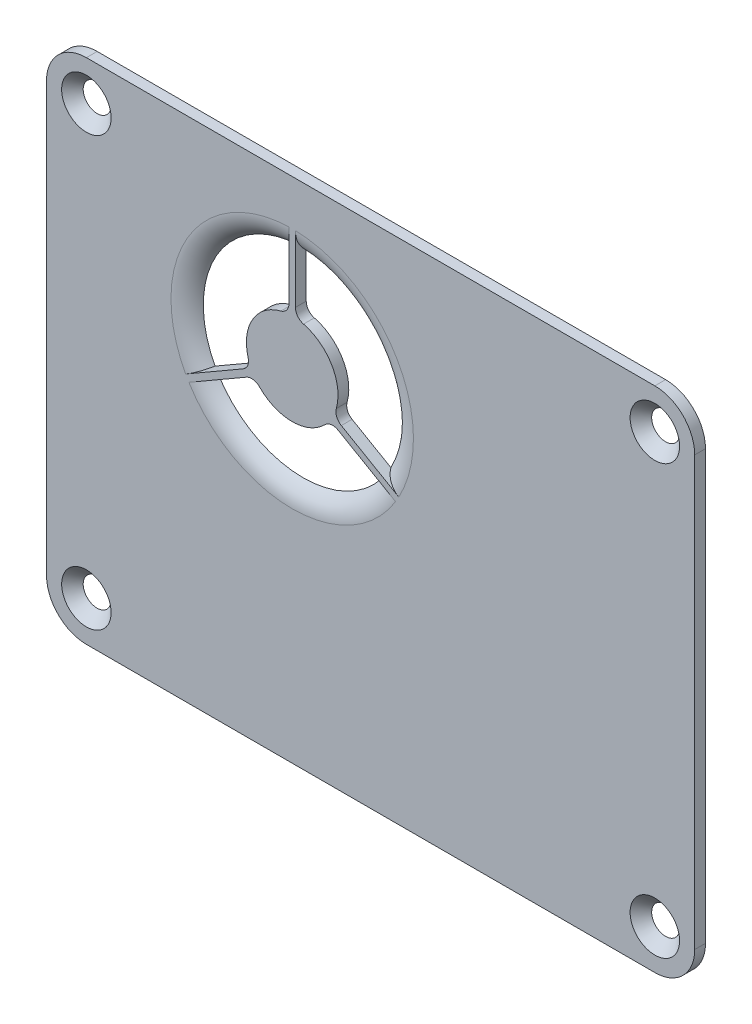
SolidWorks part; units mm, degrees
ref_plane "Alzado" through (0, 0, 0) normal (0, 0, 1) x (1, 0, 0)
ref_plane "Planta" through (0, 0, 0) normal (0, 1, 0) x (1, 0, 0)
ref_plane "Vista lateral" through (0, 0, 0) normal (1, 0, 0) x (0, 0, -1)
sketch "Sketch1" plane through (0, 0, 0) normal (0, 0, 1) x (1, 0, 0)
  line L5 (-42.95, -46.3938) -> (62.55, -46.3938) construction
  line L24 (69.95, -38.9938) -> (69.95, 40.5062) construction
  line L25 (62.55, 47.9062) -> (11.0705, 47.9062) construction
  line L26 (-23.5705, 47.9062) -> (-42.95, 47.9062) construction
  line L27 (-50.35, 40.5062) -> (-50.35, -38.9938) construction
  line L28 (-42.95, -46.3938) -> (62.55, -46.3938)
  line L29 (69.95, -38.9938) -> (69.95, 40.5062)
  line L30 (62.55, 47.9062) -> (11.0705, 47.9062)
  line L34 (-23.5705, 47.9062) -> (-42.95, 47.9062)
  line L35 (-50.35, 40.5062) -> (-50.35, -38.9938)
  line L36 (-23.5705, 47.9062) -> (11.0705, 47.9062)
  line L43 (-34.25, 40) -> (-34.25, -40)
  line L44 (19.25, 42.5) -> (-31.75, 42.5)
  line L45 (21.75, -40) -> (21.75, 40)
  line L48 (-31.75, -42.5) -> (19.25, -42.5)
  line L49 (-34.25, 40) -> (-34.25, -40) construction
  line L50 (19.25, 42.5) -> (-31.75, 42.5) construction
  line L51 (21.75, -40) -> (21.75, 40) construction
  line L52 (-31.75, -42.5) -> (19.25, -42.5) construction
  circle A0 centre (-4.75, 17) radius 18.5
  arc A8 (62.55, -46.3938) -> (69.95, -38.9938) centre (62.55, -38.9938) ccw construction
  arc A11 (69.95, 40.5062) -> (62.55, 47.9062) centre (62.55, 40.5062) ccw construction
  arc A55 (-42.95, 47.9062) -> (-50.35, 40.5062) centre (-42.95, 40.5062) ccw construction
  arc A59 (-50.35, -38.9938) -> (-42.95, -46.3938) centre (-42.95, -38.9938) ccw construction
  arc A60 (62.55, -46.3938) -> (69.95, -38.9938) centre (62.55, -38.9938) ccw
  arc A61 (69.95, 40.5062) -> (62.55, 47.9062) centre (62.55, 40.5062) ccw
  arc A62 (-42.95, 47.9062) -> (-50.35, 40.5062) centre (-42.95, 40.5062) ccw
  arc A66 (-50.35, -38.9938) -> (-42.95, -46.3938) centre (-42.95, -38.9938) ccw
  circle A67 centre (62.55, 40.5062) radius 1.5 construction
  circle A68 centre (62.55, 40.5062) radius 1.5 construction
  circle A69 centre (-42.95, 40.5062) radius 1.5 construction
  circle A73 centre (-42.95, -38.9938) radius 1.5 construction
  circle A74 centre (62.55, -38.9938) radius 1.5 construction
  circle A75 centre (-42.95, 40.5062) radius 1.5 construction
  circle A76 centre (-42.95, -38.9938) radius 1.5 construction
  circle A80 centre (62.55, -38.9938) radius 1.5 construction
  circle A81 centre (-42.95, 40.5062) radius 2.125
  circle A82 centre (-42.95, -38.9938) radius 2.125
  circle A83 centre (62.55, 40.5062) radius 2.125
  circle A87 centre (62.55, -38.9938) radius 2.125
  arc A95 (-31.75, 42.5) -> (-34.25, 40) centre (-31.75, 40) ccw
  arc A96 (21.75, 40) -> (19.25, 42.5) centre (19.25, 40) ccw
  arc A97 (19.25, -42.5) -> (21.75, -40) centre (19.25, -40) ccw
  arc A101 (-34.25, -40) -> (-31.75, -42.5) centre (-31.75, -40) ccw
  arc A102 (-31.75, 42.5) -> (-34.25, 40) centre (-31.75, 40) ccw construction
  arc A103 (21.75, 40) -> (19.25, 42.5) centre (19.25, 40) ccw construction
  arc A104 (19.25, -42.5) -> (21.75, -40) centre (19.25, -40) ccw construction
  arc A108 (-34.25, -40) -> (-31.75, -42.5) centre (-31.75, -40) ccw construction
  point P12 (-4.75, 17)
  point P46 (0, 0)
  dimension "D3" = 0
  dimension "D1" = 37
  dimension "D2" = 4.25
  dimension "D4" = 25.5
  dimension "D5" = 26.5
extrude "Main" add sketch "Sketch1" against normal blind 2
fillet "Inlet Fillet" radius 5 1 edges at (13.75, 17, 0)
sketch "Sketch20" plane through (0, 0, 0) normal (0, 0, 1) x (1, 0, 0)
  line L0 (-4.75, 25.5) -> (-4.75, 39.5) construction
  line L1 (2.6112, 12.75) -> (14.7356, 5.75) construction
  line L2 (-12.1112, 12.75) -> (-24.2356, 5.75) construction
  line L3 (-4.15, 25.4788) -> (-4.15, 39.492)
  line L22 (2.2929, 12.241) -> (14.4286, 5.2344)
  line L23 (-12.3929, 13.2802) -> (-24.5286, 6.2736)
  line L24 (-5.35, 25.4788) -> (-5.35, 39.492)
  line L25 (2.8929, 13.2802) -> (15.0286, 6.2736)
  line L26 (-11.7929, 12.241) -> (-23.9286, 5.2344)
  line L27 (-4.45, 16.4804) -> (-29.9402, 1.7636) construction
  line L28 (-5.05, 16.4804) -> (18.6, 2.826) construction
  line L29 (-5.05, 17.5196) -> (-30.5402, 2.8028) construction
  line L30 (-5.35, 17) -> (-5.35, 44.6646) construction
  line L31 (-4.45, 17.5196) -> (19.2, 3.8653) construction
  line L32 (-4.15, 17) -> (-4.15, 44.6646) construction
  line L33 (-4.75, 17) -> (-4.75, 44.6646) construction
  line L34 (-4.75, 17) -> (18.9, 3.3456) construction
  line L35 (-4.75, 17) -> (-30.2402, 2.2832) construction
  circle A0 centre (-4.75, 17) radius 8.5
  circle A2 centre (-4.75, 17) radius 22.5 construction
  circle A5 centre (-4.75, 17) radius 22.5
  dimension "D5" = 17
  dimension "D1" = 120
  dimension "D2" = 120
  dimension "D3" = 0.6
  dimension "D4" = 0.6
extrude "Fan Protection Ribs" add sketch "Sketch20" against normal through all contours A0 | A0 L3 L24 | A0 L22 L25 | A0 L23 L26 region at (-4.75, 32.4951, 0) region at (-4.75, 17, 0) region at (8.6692, 9.2524, 0) region at (-18.1692, 9.2524, 0)
fillet "Fan Protection Ribs Fillets" radius 2 6 edges at (2.2929, 12.241, -1) (2.8929, 13.2802, -1) (-4.15, 25.4788, -1) (-5.35, 25.4788, -1) (-12.3929, 13.2802, -1) (-11.7929, 12.241, -1)
hole_wizard "CSK for M4 Hex Socket Countersunk Head Screw3" positions "3DSketch3" profile "Sketch23" countersink size "M4" standard "DIN" end condition up to next
sketch3d "3DSketch3"
  line L7 (-42.95, -38.9938, -2) -> (-42.95, -38.9938, 0) construction
  line L8 (-42.95, 40.5062, -2) -> (-42.95, 40.5062, 0) construction
  line L9 (62.55, 40.5062, -2) -> (62.55, 40.5062, 0) construction
  line L10 (62.55, -38.9938, -2) -> (62.55, -38.9938, 0) construction
  point P0 (-42.95, 40.5062, 0)
  point P6 (-42.95, -38.9938, 0)
  point P10 (62.55, 40.5062, 0)
  point P14 (62.55, -38.9938, 0)
  point P32 (0, 0, 0)
  point P33 (-42.95, -38.9938, 0)
  point P36 (0, 0, 0)
  point P37 (-42.95, 40.5062, 0)
  point P40 (0, 0, 0)
  point P41 (62.55, 40.5062, 0)
  point P44 (0, 0, 0)
  point P45 (62.55, -38.9938, 0)
sketch "Sketch23" plane through (-42.95, 40.5062, 0) normal (1, 0, 0) x (0, -1, 0)
  line L0 (0, 0) -> (0, 2)
  line L1 (0, 2) -> (2.15, 2)
  line L2 (2.15, 2) -> (2.15, 2.44)
  line L3 (2.15, 2.44) -> (4.59, 0)
  line L5 (4.59, 0) -> (0, 0)
  line L6 (-2.15, 2.44) -> (-4.59, 0) construction
  line L11 (0, -6.35) -> (0, 107.95) construction
  dimension "Thru Hole Dia." = 4.3
  dimension "Thru Hole Depth" = 2
  dimension "Near C'Sink Dia." = 9.18
  dimension "Near C'Sink Angle" = 90
equation "\"D2@Sketch20\"=\"D1@Sketch20\""
